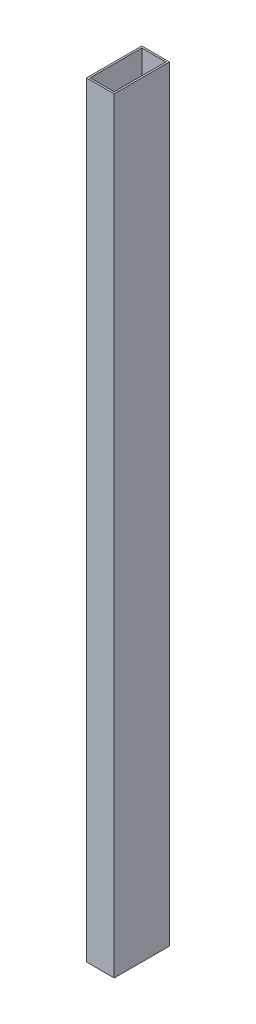
SolidWorks part; units mm, degrees
material "6061-T6 (SS)"
ref_plane "Front" through (0, 0, 0) normal (0, 0, 1) x (1, 0, 0)
ref_plane "Top" through (0, 0, 0) normal (0, 1, 0) x (1, 0, 0)
ref_plane "Right" through (0, 0, 0) normal (1, 0, 0) x (0, 0, -1)
sketch "Sketch1" plane through (0, 0, 0) normal (0, 1, 0) x (1, 0, 0)
  line L1 (12.7, 25.4) -> (-12.7, 25.4)
  line L2 (12.7, 25.4) -> (12.7, -25.4)
  line L3 (12.7, -25.4) -> (-12.7, -25.4)
  line L4 (-12.7, 25.4) -> (-12.7, -25.4)
  line L5 (12.7, 25.4) -> (-12.7, -25.4) construction
  line L6 (12.7, -25.4) -> (-12.7, 25.4) construction
  point P0 (0, 0)
  dimension "D1" = 25.4
  dimension "D2" = 50.8
extrude "Extrude-Thin1" add sketch "Sketch1" along normal blind 704.85 thin thin type one direction reverse wall 1.5875
